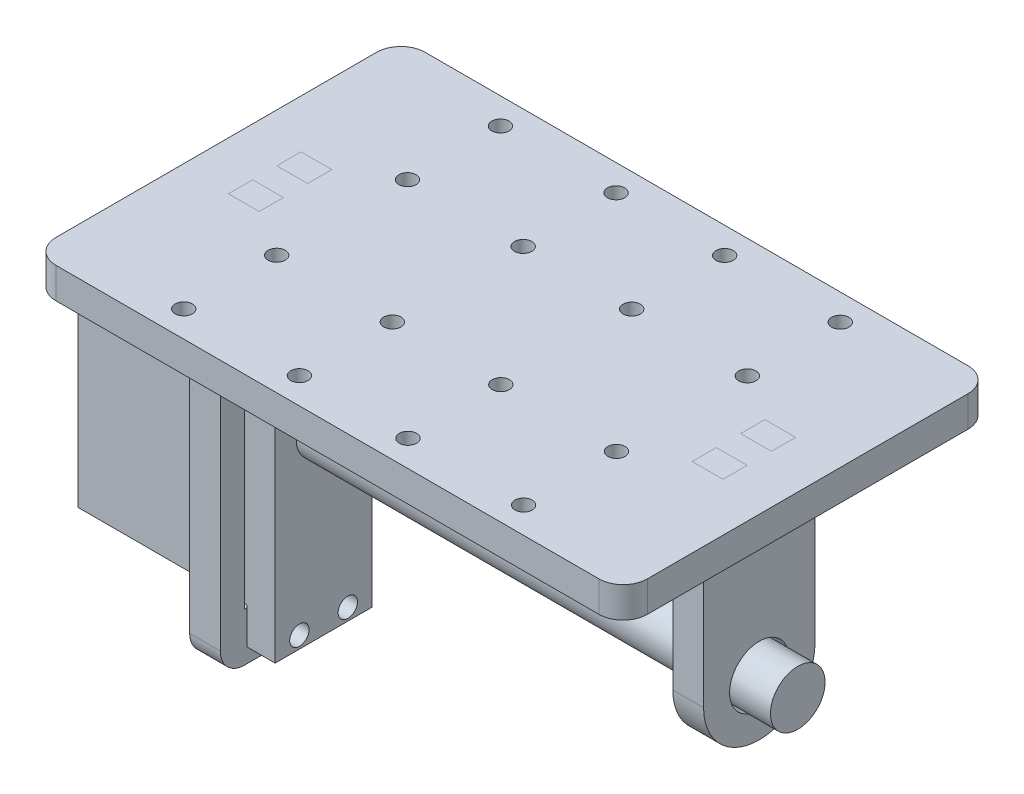
SolidWorks part; units mm, degrees
note: The reader was unsure of these and kept them because the rebuilt part matched: shared geometry of "Sketch1<3>", "Sketch1<4>".
ref_plane "Front Plane" through (0, 0, 0) normal (0, 0, 1) x (1, 0, 0)
ref_plane "Top Plane" through (0, 0, 0) normal (0, 1, 0) x (1, 0, 0)
ref_plane "Right Plane" through (0, 0, 0) normal (1, 0, 0) x (0, 0, -1)
sketch "Sketch1" plane through (0, 0, 0) normal (1, 0, 0) x (0, 0, -1)
  line L0 (20, 40) -> (20, 47.5)
  line L1 (0, 0) -> (20, 0)
  line L2 (0, 0) -> (0, 40)
  line L3 (0, 40) -> (20, 40)
  line L4 (20, 0) -> (20, 40)
  line L5 (20, 47.5) -> (0, 47.5)
  line L6 (0, 47.5) -> (0, 40)
  line L7 (0, 0) -> (0, -7.5)
  line L8 (0, -7.5) -> (20, -7.5)
  line L9 (20, -7.5) -> (20, 0)
  line L10 (10, 47.5) -> (10, -7.5) construction
  circle A0 centre (10, 30.25) radius 5.64
  circle A1 centre (5, 45) radius 2
  circle A2 centre (5, -5) radius 2
  circle A3 centre (15, 45) radius 2
  circle A4 centre (15, -5) radius 2
  dimension "D1" = 11.28
  dimension "D10" = 4
  dimension "D11" = 4
  dimension "D8" = 5
  dimension "D2" = 40
  dimension "D3" = 20
  dimension "D4" = 9.75
  dimension "D5" = 10
  dimension "D6" = 7.5
  dimension "D7" = 7.5
  dimension "D9" = 5
  dimension "D12" = 5
extrude "Boss-Extrude2" add sketch "Sketch1" against normal blind 37 and the other way blind 3.7
extrude "Boss-Extrude3" add sketch "Sketch1<3>" along normal blind 101.6
sketch "Sketch1<3>" plane through (0, 0, 0) normal (1, 0, 0) x (0, 0, -1) same geometry as "Sketch1"
ref_plane "Plane2" through (87.3, 0, 0) normal (1, 0, 0) x (0, 0, -1)
ref_plane "Plane3" through (-2.1, 0, 0) normal (1, 0, 0) x (0, 0, -1)
sketch "Sketch2" plane through (87.3, 0, 0) normal (1, 0, 0) x (0, 0, -1)
  line L1 (0, 40) -> (20, 40) construction
  line L2 (21.5, 30.25) -> (21.5, 40)
  line L3 (-1.5, 30.25) -> (-1.5, 40)
  line L4 (-1.5, 40) -> (-1.5, 62.75)
  line L6 (21.5, 62.75) -> (21.5, 40)
  line L8 (17.5, 69.1) -> (12.5, 69.1)
  line L9 (12.5, 69.1) -> (12.5, 62.75)
  line L15 (7.5, 62.75) -> (7.5, 69.1)
  line L16 (7.5, 69.1) -> (2.5, 69.1)
  line L19 (12.5, 62.75) -> (7.5, 62.75)
  line L20 (17.5, 69.1) -> (17.5, 62.75)
  line L21 (17.5, 62.75) -> (21.5, 62.75)
  line L22 (2.5, 69.1) -> (2.5, 62.75)
  line L23 (2.5, 62.75) -> (-1.5, 62.75)
  circle A1 centre (10, 30.25) radius 5.64 construction
  arc A2 (-1.5, 30.25) -> (21.5, 30.25) centre (10, 30.25) ccw
  circle A3 centre (10, 30.25) radius 6.14
  dimension "D1" = 32.5
  dimension "D6" = 0.5
  dimension "D2" = 6.35
  dimension "D3" = 23
  dimension "D4" = 5
  dimension "D5" = 5
  dimension "D7" = 5
  dimension "D8" = 4
extrude "Boss-Extrude4" add sketch "Sketch2" along normal blind 6.35 separate body
sketch "Sketch3" plane through (-2.1, 0, 0) normal (1, 0, 0) x (0, 0, -1)
  line L0 (20.5, 40.5) -> (-0.5, 40.5)
  line L1 (-0.5, 40.5) -> (-0.5, -0.5)
  line L2 (-0.5, -0.5) -> (20.5, -0.5)
  line L3 (20.5, -0.5) -> (20.5, 40.5)
  line L9 (-5.5, 62.75) -> (-5.5, -5.5)
  line L10 (-0.5, -10.5) -> (20.5, -10.5)
  line L11 (25.5, -5.5) -> (25.5, 62.75)
  line L13 (10, 47.5) -> (10, -7.5) construction
  line L14 (-0.5, 20) -> (-5.5, 20) construction
  line L15 (20.5, 20) -> (25.5, 20) construction
  line L27 (20, 0) -> (20, 40) construction
  line L28 (0, 40) -> (20, 40) construction
  line L29 (0, 0) -> (20, 0) construction
  line L30 (0, 0) -> (0, 40) construction
  line L31 (25.5, 62.75) -> (17.5, 62.75)
  line L32 (17.5, 62.75) -> (17.5, 69.1)
  line L33 (17.5, 69.1) -> (12.5, 69.1)
  line L34 (17.5, 69.1) -> (12.5, 69.1) construction
  line L35 (12.5, 69.1) -> (12.5, 62.75)
  line L36 (12.5, 62.75) -> (7.5, 62.75)
  line L37 (7.5, 62.75) -> (7.5, 69.1)
  line L38 (7.5, 69.1) -> (2.5, 69.1)
  line L39 (2.5, 69.1) -> (2.5, 62.75)
  line L40 (2.5, 62.75) -> (-5.5, 62.75)
  arc A0 (-0.5, -10.5) -> (-5.5, -5.5) centre (-0.5, -5.5) cw
  arc A1 (25.5, -5.5) -> (20.5, -10.5) centre (20.5, -5.5) cw
  circle A4 centre (5, -5) radius 2
  circle A5 centre (5, 45) radius 2
  circle A6 centre (5, 45) radius 2 construction
  circle A7 centre (5, -5) radius 2 construction
  circle A8 centre (15, 45) radius 2
  circle A9 centre (15, -5) radius 2
  dimension "D8" = 5
  dimension "D9" = 5
  dimension "D4" = 0.5
  dimension "D5" = 0.5
  dimension "D1" = 5
  dimension "D2" = 10
  dimension "D3" = 5
  dimension "D6" = 0.5
  dimension "D7" = 0.5
extrude "Boss-Extrude5" add sketch "Sketch3" against normal blind 6.35
extrude "Boss-Extrude8" add sketch "Sketch1<4>" against normal blind 2.1 and the other way blind 3.7 contours L5 L6 L3 L0 | L8 L9 L1 L7 | L1 L10 L8 L9 A4 | L5 L10 L3 L0 A3
sketch "Sketch1<4>" plane through (0, 0, 0) normal (1, 0, 0) x (0, 0, -1) same geometry as "Sketch1"
sketch "Sketch7" plane through (0, 62.75, 0) normal (0, 1, 0) x (1, 0, 0)
  line L0 (-13.45, 48.1) -> (98.65, 48.1)
  line L5 (103.65, 43.1) -> (103.65, -23.1)
  line L6 (98.65, -28.1) -> (-13.45, -28.1)
  line L7 (-18.45, -23.1) -> (-18.45, 43.1)
  line L12 (93.65, 17.5) -> (93.65, 12.5) construction
  line L23 (93.65, 12.5) -> (87.3, 12.5)
  line L28 (87.3, 7.5) -> (93.65, 7.5)
  line L32 (-8.45, 12.5) -> (-8.45, 7.5) construction
  line L33 (93.65, 12.5) -> (93.65, 17.5)
  line L34 (93.65, 17.5) -> (87.3, 17.5)
  line L35 (87.3, 17.5) -> (87.3, 12.5)
  line L38 (87.3, 2.5) -> (87.3, 7.5)
  line L39 (-8.45, 17.5) -> (-2.1, 17.5)
  line L40 (-2.1, 17.5) -> (-2.1, 12.5)
  line L41 (-2.1, 12.5) -> (-8.45, 12.5)
  line L42 (-8.45, 12.5) -> (-8.45, 17.5)
  line L43 (-2.1, 7.5) -> (-2.1, 2.5)
  line L44 (-2.1, 2.5) -> (-8.45, 2.5)
  line L45 (-8.45, 2.5) -> (-8.45, 7.5)
  line L46 (-8.45, 7.5) -> (-2.1, 7.5)
  line L47 (7.522, -22.691) -> (31.398, -22.691) construction
  line L48 (42.6, 33.1) -> (42.6, -13.1) construction
  line L49 (65.74, -13.1) -> (19.46, -13.1) construction
  line L50 (7.522, -3.509) -> (31.398, -3.509) construction
  line L51 (77.678, -22.691) -> (53.802, -22.691) construction
  line L52 (19.46, -3.509) -> (19.46, -22.691) construction
  line L53 (65.74, -3.509) -> (65.74, -22.691) construction
  line L54 (93.65, 7.5) -> (93.65, 2.5)
  line L55 (93.65, 2.5) -> (87.3, 2.5)
  line L56 (77.678, -3.509) -> (53.802, -3.509) construction
  line L57 (24.538, 10) -> (60.662, 10) construction
  line L58 (7.522, 42.691) -> (31.398, 42.691) construction
  line L59 (7.522, 23.509) -> (31.398, 23.509) construction
  line L60 (19.46, 23.509) -> (19.46, 42.691) construction
  line L61 (77.678, 42.691) -> (53.802, 42.691) construction
  line L62 (77.678, 23.509) -> (53.802, 23.509) construction
  line L63 (65.74, 23.509) -> (65.74, 42.691) construction
  line L64 (65.74, 33.1) -> (19.46, 33.1) construction
  arc A0 (98.65, 48.1) -> (103.65, 43.1) centre (98.65, 43.1) cw
  arc A2 (-13.45, 48.1) -> (-18.45, 43.1) centre (-13.45, 43.1) ccw
  arc A3 (-18.45, -23.1) -> (-13.45, -28.1) centre (-13.45, -23.1) ccw
  arc A4 (98.65, -28.1) -> (103.65, -23.1) centre (98.65, -23.1) ccw
  circle A5 centre (31.398, -22.691) radius 1.778
  circle A6 centre (7.522, -22.691) radius 1.778
  circle A7 centre (7.522, -3.509) radius 1.778
  circle A8 centre (31.398, -3.509) radius 1.778
  circle A9 centre (77.678, -22.691) radius 1.778
  circle A10 centre (53.802, -22.691) radius 1.778
  circle A11 centre (53.802, -3.509) radius 1.778
  circle A12 centre (77.678, -3.509) radius 1.778
  circle A13 centre (31.398, 42.691) radius 1.778
  circle A14 centre (7.522, 42.691) radius 1.778
  circle A15 centre (7.522, 23.509) radius 1.778
  circle A16 centre (31.398, 23.509) radius 1.778
  circle A17 centre (77.678, 42.691) radius 1.778
  circle A18 centre (53.802, 42.691) radius 1.778
  circle A19 centre (53.802, 23.509) radius 1.778
  circle A20 centre (77.678, 23.509) radius 1.778
  point P24 (19.46, -22.691)
  point P31 (19.46, -3.509)
  point P33 (19.46, -13.1)
  point P39 (42.6, 10)
  point P78 (42.6, 10)
  dimension "D5" = 5
  dimension "D6" = 5
  dimension "D13" = 3.556
  dimension "D14" = 3.556
  dimension "D15" = 3.556
  dimension "D16" = 3.556
  dimension "D1" = 44.7
  dimension "D2" = 46.2
  dimension "D3" = 10
  dimension "D4" = 10
  dimension "D7" = 15
  dimension "D8" = 23.14
  dimension "D9" = 19.182
  dimension "D10" = 23.876
  dimension "D11" = 2.5
  dimension "D12" = 15
extrude "Boss-Extrude11" add sketch "Sketch7" along normal blind 6.35 separate body
